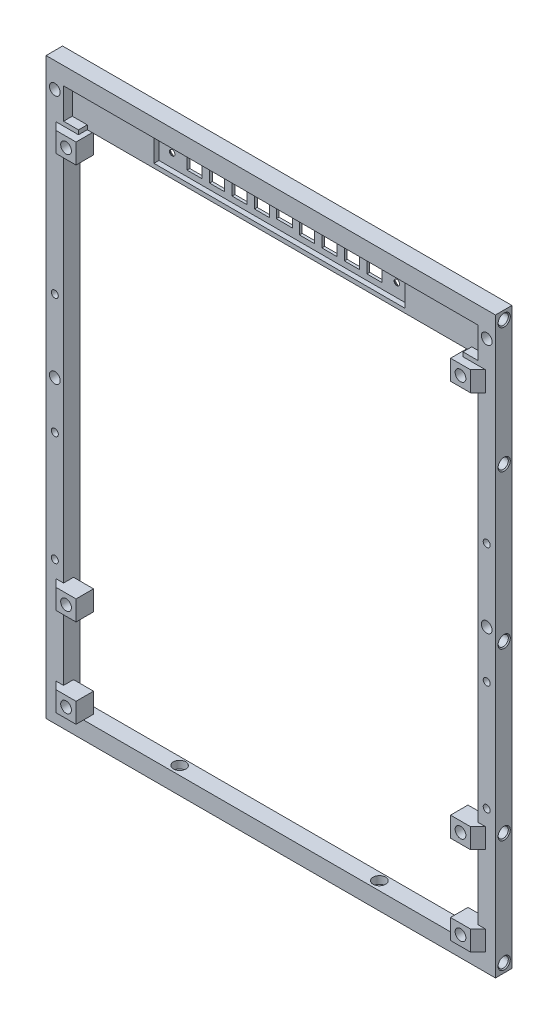
SolidWorks part; units mm, degrees
ref_plane "Front Plane" through (0, 0, 0) normal (0, 0, 1) x (1, 0, 0)
ref_plane "Top Plane" through (0, 0, 0) normal (0, 1, 0) x (1, 0, 0)
ref_plane "Right Plane" through (0, 0, 0) normal (1, 0, 0) x (0, 0, -1)
sketch "Sketch1" plane through (0, 0, 0) normal (0, 0, 1) x (1, 0, 0)
  line L1 (-90, -115) -> (90, -115)
  line L2 (-90, -115) -> (-90, 115)
  line L3 (-90, 115) -> (90, 115)
  line L4 (90, -115) -> (90, 115)
  line L5 (-90, -115) -> (90, 115) construction
  line L6 (-90, 115) -> (90, -115) construction
  line L7 (-83, -108) -> (83, -108)
  line L8 (-83, -108) -> (-83, 108)
  line L9 (-83, 108) -> (83, 108)
  line L10 (83, -108) -> (83, 108)
  line L11 (-83, -108) -> (83, 108) construction
  line L12 (-83, 108) -> (83, -108) construction
  point P0 (0, 0)
  point P6 (0, 0)
  dimension "D1" = 180
  dimension "D2" = 230
  dimension "D3" = 7
  dimension "D4" = 7
extrude "Boss-Extrude1" add sketch "Sketch1" along normal blind 7
sketch "Sketch2" plane through (-90, 0, 0) normal (-1, 0, 0) x (0, 0, 1)
  line L0 (3.5, 111.5) -> (3.5, -111.5) construction
  line L1 (7, 115) -> (0, 115) construction
  circle A0 centre (3.5, -111.5) radius 2.05
  circle A2 centre (3.5, 111.5) radius 2.05
  circle A3 centre (3.5, 61.5) radius 2.05
  circle A4 centre (3.5, -66.5) radius 2.05
  point P2 (3.5, 0)
  point P7 (3.5, 115)
  dimension "D2" = 4.1
  dimension "D3" = 50
  dimension "D4" = 45
  dimension "D1" = 3.5
extrude "Cut-Extrude1" cut sketch "Sketch2" against normal blind 6
mirror "Mirror1" about plane through (0, 0, 0) normal (1, 0, 0) of "Cut-Extrude1"
sketch "Sketch3" plane through (0, -108, 0) normal (0, 1, 0) x (1, 0, 0)
  line L0 (0, 0) -> (0, -7) construction
  line L1 (-83, 0) -> (83, 0) construction
  line L2 (-83, -7) -> (83, -7) construction
  line L3 (40, -3.5) -> (-40, -3.5) construction
  circle A0 centre (40, -3.5) radius 1.35
  circle A1 centre (-40, -3.5) radius 1.35
  point P9 (0, -3.5)
  dimension "D1" = 2.7
  dimension "D2" = 80
extrude "Cut-Extrude2" cut sketch "Sketch3" against normal through all
sketch "Sketch4" plane through (0, -108, 0) normal (0, 1, 0) x (1, 0, 0)
  circle A0 centre (40, -3.5) radius 2.5
  circle A1 centre (-40, -3.5) radius 2.5
  dimension "D1" = 5
extrude "Cut-Extrude3" cut sketch "Sketch4" against normal blind 3
sketch "Sketch5" plane through (0, 0, 0) normal (0, 0, -1) x (-1, 0, 0)
  line L0 (-86.5, -115) -> (-86.5, 115) construction
  line L1 (90, -115) -> (-90, -115) construction
  line L2 (-90, 115) -> (90, 115) construction
  line L3 (-83, 0) -> (-90, 0) construction
  line L4 (-83, -108) -> (-83, 108) construction
  line L5 (-90, -115) -> (-90, 115) construction
  line L6 (0, 115) -> (0, -115) construction
  line L7 (83, -108) -> (-83, -108) construction
  circle A0 centre (-86.5, 34) radius 1.4
  circle A1 centre (86.5, 34) radius 1.4
  circle A2 centre (-86.5, -58) radius 1.4
  circle A3 centre (86.5, -58) radius 1.4
  point P12 (-86.5, 0)
  point P13 (-86.5, 0)
  dimension "D1" = 2.8
  dimension "D2" = 34
  dimension "D3" = 50
extrude "Cut-Extrude4" cut sketch "Sketch5" against normal through all
sketch "Sketch6" plane through (0, 0, 0) normal (0, 0, -1) x (-1, 0, 0)
  circle A0 centre (-86.5, 34) radius 2.5
  circle A1 centre (86.5, 34) radius 2.5
  circle A2 centre (-86.5, -58) radius 2.5
  circle A3 centre (86.5, -58) radius 2.5
  dimension "D1" = 5
extrude "Cut-Extrude5" cut sketch "Sketch6" against normal blind 3
sketch "Sketch7" plane through (0, 0, 0) normal (0, 0, -1) x (-1, 0, 0)
  line L0 (-83, 108) -> (-90, 108) construction
  line L1 (-90, -115) -> (-90, 115) construction
  line L2 (-86.5, 105) -> (-86.5, 5) construction
  line L3 (-90, 115) -> (90, 115) construction
  circle A0 centre (-86.5, 105) radius 2.15
  circle A1 centre (-86.5, 5) radius 2.15
  point P8 (-86.5, 108)
  dimension "D1" = 4.3
  dimension "D2" = 10
  dimension "D3" = 100
extrude "Cut-Extrude6" cut sketch "Sketch7" against normal through all
mirror "Mirror2" about plane through (0, 0, 0) normal (1, 0, 0) of "Cut-Extrude6"
sketch "Sketch8" plane through (0, 0, 3) normal (0, 0, -1) x (-1, 0, 0)
  line L2 (-87.9, 31.9288) -> (-87.9, 36.0712)
  line L4 (-85.1, 31.9288) -> (-85.1, 36.0712)
  line L5 (-87.9, 31.9288) -> (-85.1, 36.0712) construction
  line L6 (-87.9, 36.0712) -> (-85.1, 31.9288) construction
  line L8 (-87.9, -60.0712) -> (-87.9, -55.9288)
  line L10 (-85.1, -60.0712) -> (-85.1, -55.9288)
  line L11 (-87.9, -60.0712) -> (-85.1, -55.9288) construction
  line L12 (-87.9, -55.9288) -> (-85.1, -60.0712) construction
  circle A0 centre (-86.5, 34) radius 2.5 construction
  circle A1 centre (-86.5, -58) radius 2.5 construction
  circle A2 centre (-86.5, -58) radius 2.5 construction
  arc A3 (-85.1, 36.0712) -> (-87.9, 36.0712) centre (-86.5, 34) ccw
  arc A4 (-85.1, -55.9288) -> (-87.9, -55.9288) centre (-86.5, -58) ccw
  circle A5 centre (-86.5, 34) radius 1.4 construction
  circle A6 centre (-86.5, -58) radius 1.4 construction
  arc A7 (-87.9, -60.0712) -> (-85.1, -60.0712) centre (-86.5, -58) ccw
  arc A8 (-87.9, 31.9288) -> (-85.1, 31.9288) centre (-86.5, 34) ccw
  point P0 (-86.5, 34)
  point P8 (-86.5, -58)
extrude "Cut-Extrude7" cut sketch "Sketch8" against normal blind 0.2
sketch "Sketch9" plane through (0, 0, 3.2) normal (0, 0, -1) x (-1, 0, 0)
  line L0 (-85.1, 34) -> (-85.1, 36.0712) construction
  line L1 (-87.9, 32.6) -> (-85.1, 32.6)
  line L2 (-87.9, 32.6) -> (-87.9, 35.4)
  line L3 (-87.9, 35.4) -> (-85.1, 35.4)
  line L4 (-85.1, 32.6) -> (-85.1, 35.4)
  line L5 (-87.9, 32.6) -> (-85.1, 35.4) construction
  line L6 (-87.9, 35.4) -> (-85.1, 32.6) construction
  line L7 (-85.1, -60.0712) -> (-85.1, -55.9288) construction
  line L8 (-87.9, -59.4) -> (-85.1, -59.4)
  line L9 (-87.9, -59.4) -> (-87.9, -56.6)
  line L10 (-87.9, -56.6) -> (-85.1, -56.6)
  line L11 (-85.1, -59.4) -> (-85.1, -56.6)
  line L12 (-87.9, -59.4) -> (-85.1, -56.6) construction
  line L13 (-87.9, -56.6) -> (-85.1, -59.4) construction
  arc A0 (-85.1, 34) -> (-87.9, 34) centre (-86.5, 34) ccw construction
  point P0 (-86.5, 34)
  point P8 (-86.5, -58)
extrude "Cut-Extrude8" cut sketch "Sketch9" against normal blind 0.2
mirror "Mirror3" about plane through (0, 0, 0) normal (1, 0, 0) of "Cut-Extrude8", "Cut-Extrude7"
sketch "Sketch10" plane through (0, 0, 7) normal (0, 0, 1) x (1, 0, 0)
  line L0 (83, -108) -> (83, 108) construction
  line L1 (83, -108) -> (77, -108)
  line L2 (83, -108) -> (83, -102)
  line L3 (83, -102) -> (77, -102)
  line L4 (77, -108) -> (77, -102)
  line L5 (83, -78.5) -> (77, -78.5)
  line L6 (83, -78.5) -> (83, -72.5)
  line L7 (83, -72.5) -> (77, -72.5)
  line L8 (77, -78.5) -> (77, -72.5)
  line L9 (-83, -108) -> (83, -108) construction
  dimension "D1" = 6
  dimension "D2" = 35.5
extrude "Boss-Extrude2" add sketch "Sketch10" against normal offset from surface (5.5 mm away) 1.5 up to face at (-84.35, 5, 0)
sketch "Sketch11" plane through (0, 0, 1.5) normal (0, 0, -1) x (-1, 0, 0)
  line L0 (-83, -78.5) -> (-77, -72.5) construction
  line L2 (-83, -108) -> (-77, -102) construction
  circle A0 centre (-80, -75.5) radius 1.65
  circle A1 centre (-80, -105) radius 1.65
  dimension "D1" = 3.3
extrude "Cut-Extrude9" cut sketch "Sketch11" against normal through all
mirror "Mirror4" about plane through (0, 0, 0) normal (1, 0, 0) of "Cut-Extrude9", "Boss-Extrude2"
sketch "Sketch12" plane through (0, 0, 0) normal (0, 0, -1) x (-1, 0, 0)
  line L0 (83, 108) -> (83, -108) construction
  line L1 (-83, 108) -> (83, 108)
  line L2 (-83, 108) -> (-83, 94)
  line L3 (-83, 94) -> (83, 94)
  line L4 (83, 108) -> (83, 94)
  dimension "D1" = 14
extrude "Boss-Extrude3" add sketch "Sketch12" against normal blind 1.5
sketch "Sketch13" plane through (0, 0, 1.5) normal (0, 0, 1) x (1, 0, 0)
  line L0 (-83, 108) -> (83, 94) construction
  line L2 (-50.3, 95.7) -> (50.3, 95.7)
  line L3 (-50.3, 95.7) -> (-50.3, 106.3)
  line L4 (-50.3, 106.3) -> (50.3, 106.3)
  line L5 (50.3, 95.7) -> (50.3, 106.3)
  line L6 (-50.3, 95.7) -> (50.3, 106.3) construction
  line L7 (-50.3, 106.3) -> (50.3, 95.7) construction
  line L8 (-83, 94) -> (83, 94)
  line L9 (-83, 94) -> (-83, 108)
  line L10 (-83, 108) -> (83, 108)
  line L11 (83, 94) -> (83, 108)
  line L12 (-83, 94) -> (83, 108) construction
  line L13 (-83, 108) -> (83, 94) construction
  point P4 (0, 101)
  point P9 (0, 101)
  dimension "D1" = 100.6
  dimension "D2" = 10.6
extrude "Boss-Extrude4" add sketch "Sketch13" along normal blind 2
sketch "Sketch14" plane through (0, 0, 1.5) normal (0, 0, 1) x (1, 0, 0)
  line L0 (0, 106.3) -> (0, 95.7) construction
  line L1 (50.3, 106.3) -> (-50.3, 106.3) construction
  line L2 (-50.3, 95.7) -> (50.3, 95.7) construction
  line L3 (-50.3, 101) -> (50.3, 101) construction
  line L4 (50.3, 95.7) -> (50.3, 106.3) construction
  line L5 (-33, 104) -> (-39, 104)
  line L6 (-3.25, 99) -> (3.25, 99)
  line L7 (-3.25, 99) -> (-3.25, 103)
  line L8 (-3.25, 103) -> (3.25, 103)
  line L9 (3.25, 99) -> (3.25, 103)
  line L10 (-3.25, 99) -> (3.25, 103) construction
  line L11 (-3.25, 103) -> (3.25, 99) construction
  line L12 (6, 98) -> (12, 98)
  line L13 (6, 98) -> (6, 104)
  line L14 (6, 104) -> (12, 104)
  line L15 (12, 98) -> (12, 104)
  line L16 (6, 98) -> (12, 104) construction
  line L17 (6, 104) -> (12, 98) construction
  line L18 (15, 98) -> (21, 98)
  line L19 (15, 98) -> (15, 104)
  line L20 (15, 104) -> (21, 104)
  line L21 (21, 98) -> (21, 104)
  line L22 (15, 98) -> (21, 104) construction
  line L23 (15, 104) -> (21, 98) construction
  line L24 (24, 98) -> (30, 98)
  line L25 (24, 98) -> (24, 104)
  line L26 (24, 104) -> (30, 104)
  line L27 (30, 98) -> (30, 104)
  line L28 (24, 98) -> (30, 104) construction
  line L29 (24, 104) -> (30, 98) construction
  line L30 (33, 98) -> (39, 98)
  line L31 (33, 98) -> (33, 104)
  line L32 (33, 104) -> (39, 104)
  line L33 (39, 98) -> (39, 104)
  line L34 (33, 98) -> (39, 104) construction
  line L35 (33, 104) -> (39, 98) construction
  line L36 (-39, 98) -> (-39, 104)
  line L37 (-33, 98) -> (-39, 98)
  line L38 (-33, 98) -> (-33, 104)
  line L39 (-24, 104) -> (-30, 104)
  line L40 (-30, 98) -> (-30, 104)
  line L41 (-24, 98) -> (-30, 98)
  line L42 (-24, 98) -> (-24, 104)
  line L43 (-15, 104) -> (-21, 104)
  line L44 (-21, 98) -> (-21, 104)
  line L45 (-15, 98) -> (-21, 98)
  line L46 (-15, 98) -> (-15, 104)
  line L47 (-6, 104) -> (-12, 104)
  line L48 (-12, 98) -> (-12, 104)
  line L49 (-6, 98) -> (-12, 98)
  line L50 (-6, 98) -> (-6, 104)
  circle A0 centre (-45, 101) radius 1.3 construction
  circle A1 centre (45, 101) radius 1.3 construction
  point P6 (0, 101)
  point P11 (0, 101)
  point P16 (9, 101)
  point P21 (18, 101)
  point P26 (27, 101)
  point P31 (36, 101)
  dimension "D10" = 2.6
  dimension "D9" = 45
  dimension "D1" = 6.5
  dimension "D2" = 4
  dimension "D3" = 6
  dimension "D4" = 9
  dimension "D5" = 9
  dimension "D6" = 9
  dimension "D7" = 9
  dimension "D8" = 45
extrude "Cut-Extrude10" cut sketch "Sketch14" against normal through all
sketch "Sketch15" plane through (0, 0, 1.5) normal (0, 0, 1) x (1, 0, 0)
  circle A0 centre (-45, 101) radius 1
  circle A1 centre (45, 101) radius 1
  dimension "D1" = 2
extrude "Boss-Extrude5" add sketch "Sketch15" along normal up to surface (2 mm away) up to face at (0, 101, 3.5)
chamfer "Chamfer1" distance 0.4 angle 45 3 edges at (-83, -7, 0) (83, -7, 0) (0, -108, 0) tangent propagation no
chamfer "Chamfer2" distance 0.4 angle 45 4 edges at (0, 115, 0) (-90, 0, 0) (0, -115, 0) (90, 0, 0)
chamfer "Chamfer3" distance 0.4 angle 45 36 edges at (-36, 98, 0) (-39, 101, 0) (-36, 104, 0) (-33, 101, 0) (-27, 98, 0) (-30, 101, 0) (-27, 104, 0) (-24, 101, 0) (-18, 98, 0) (-21, 101, 0) (-18, 104, 0) (-15, 101, 0) (-9, 98, 0) (-12, 101, 0) (-9, 104, 0) (-6, 101, 0) (0, 99, 0) (-3.25, 101, 0) (0, 103, 0) (3.25, 101, 0) (9, 98, 0) (6, 101, 0) (9, 104, 0) (12, 101, 0) (18, 98, 0) (15, 101, 0) (18, 104, 0) (21, 101, 0) (36, 98, 0) (33, 101, 0) (36, 104, 0) (39, 101, 0) (27, 98, 0) (24, 101, 0) (27, 104, 0) (30, 101, 0)
sketch "Sketch16" plane through (0, 0, 7) normal (0, 0, 1) x (1, 0, 0)
  line L0 (-77, 94) -> (-77, 95.7)
  line L1 (-83, -72.5) -> (-77, -72.5)
  line L2 (-83, -72.5) -> (-83, -66.5)
  line L3 (-83, -66.5) -> (-77, -66.5)
  line L4 (-77, -72.5) -> (-77, -66.5)
  line L5 (83, -72.5) -> (77, -72.5)
  line L6 (83, -72.5) -> (83, -66.5)
  line L7 (83, -66.5) -> (77, -66.5)
  line L8 (77, -72.5) -> (77, -66.5)
  line L9 (83, 94) -> (77, 94) construction
  line L10 (83, 94) -> (83, 88)
  line L11 (83, 88) -> (77, 88)
  line L12 (77, 94) -> (77, 88)
  line L13 (-83, 94) -> (-77, 94) construction
  line L14 (-83, 94) -> (-83, 88)
  line L15 (-83, 88) -> (-77, 88)
  line L16 (-77, 94) -> (-77, 88)
  line L17 (-50.3, 95.7) -> (50.3, 95.7) construction
  line L18 (-77, 95.7) -> (-83, 95.7)
  line L19 (-83, 108) -> (-83, 94) construction
  line L20 (-83, 95.7) -> (-83, 94)
  line L21 (77, 94) -> (77, 95.7)
  line L22 (77, 95.7) -> (83, 95.7)
  line L23 (83, 94) -> (83, 108) construction
  line L24 (83, 95.7) -> (83, 94)
  dimension "D1" = 6
extrude "Boss-Extrude7" add sketch "Sketch16" against normal offset from surface (5.5 mm away) 1.5 up to face at (-36, 101, 0)
sketch "Sketch17" plane through (0, 0, 1.5) normal (0, 0, -1) x (-1, 0, 0)
  line L0 (-77, 88) -> (77, -66.5) construction
  line L1 (-77, -66.5) -> (-77, -78.5) construction
  line L2 (-80, -69.5) -> (80, -69.5) construction
  line L3 (-80, -69.5) -> (-80, 91) construction
  line L4 (-80, 91) -> (80, 91) construction
  line L5 (80, -69.5) -> (80, 91) construction
  line L6 (-80, -69.5) -> (80, 91) construction
  line L7 (-80, 91) -> (80, -69.5) construction
  line L8 (77, -66.5) -> (83, -66.5) construction
  circle A0 centre (-80, -69.5) radius 1.65
  circle A1 centre (80, -69.5) radius 1.65
  circle A2 centre (80, 91) radius 1.65
  circle A3 centre (-80, 91) radius 1.65
  point P4 (0, 10.75)
  dimension "D3" = 3.3
  dimension "D1" = 3
  dimension "D2" = 3
extrude "Cut-Extrude11" cut sketch "Sketch17" against normal through all
sketch "Sketch18" plane through (0, 0, 1.5) normal (0, 0, 1) x (1, 0, 0)
  circle A0 centre (-45, 101) radius 1.1
  circle A1 centre (45, 101) radius 1.1
  dimension "D1" = 2.2
extrude "Cut-Extrude12" cut sketch "Sketch18" against normal through all both and the other way through all
chamfer "Chamfer4" distance 1.3 angle 45 2 edges at (-43.9, 101, 0) (46.1, 101, 0)
sketch "Sketch19" plane through (0, 0, 1.5) normal (0, 0, -1) x (-1, 0, 0)
  line L1 (-83, -108) -> (83, -108)
  line L2 (-83, -108) -> (-83, 94)
  line L3 (-83, 94) -> (83, 94)
  line L4 (83, -108) -> (83, 94)
extrude "Cut-Extrude13" cut sketch "Sketch19" against normal through all
ref_plane "Plane1" through (0, 0, 3) normal (0, 0, 1) x (1, 0, 0)
sketch "Sketch20" plane through (0, 0, 3) normal (0, 0, 1) x (1, 0, 0)
  line L0 (83, 94) -> (83, -108) construction
  line L1 (83, -108) -> (75, -108)
  line L2 (83, -108) -> (83, -100)
  line L3 (83, -100) -> (75, -100)
  line L4 (75, -108) -> (75, -100)
  line L5 (83, 94) -> (75, 94)
  line L6 (83, 94) -> (83, 86)
  line L7 (83, 86) -> (75, 86)
  line L8 (75, 94) -> (75, 86)
  line L9 (83, -64.5) -> (75, -64.5)
  line L10 (83, -64.5) -> (83, -72.5)
  line L11 (83, -72.5) -> (75, -72.5)
  line L12 (75, -64.5) -> (75, -72.5)
  dimension "D1" = 8
  dimension "D2" = 27.5
extrude "Boss-Extrude8" add sketch "Sketch20" along normal blind 7
sketch "Sketch21" plane through (0, 0, 3) normal (0, 0, -1) x (-1, 0, 0)
  line L0 (-75, 94) -> (-83, 86) construction
  line L1 (-83, -100) -> (-75, -108) construction
  line L2 (-83, -64.5) -> (-75, -72.5) construction
  circle A0 centre (-79, 90) radius 2.15
  circle A1 centre (-79, -104) radius 2.15
  circle A2 centre (-79, -68.5) radius 2.15
  dimension "D1" = 4.3
extrude "Cut-Extrude14" cut sketch "Sketch21" against normal through all
mirror "Mirror5" about plane through (0, 0, 0) normal (1, 0, 0) of "Cut-Extrude14", "Boss-Extrude8"
chamfer "Chamfer5" distance 3 angle 45 6 edges at (-83, -104, 7) (83, -104, 7) (83, 90, 7) (-83, 90, 7) (-83, -68.5, 7) (83, -68.5, 7)
sketch "Sketch23" plane through (0, 0, 0) normal (0, 0, -1) x (-1, 0, 0)
  line L0 (-83.4, 94) -> (83.4, 94) construction
  line L1 (-15, 94) -> (15, 94)
  line L2 (-15, 94) -> (-15, 69)
  line L3 (-15, 69) -> (15, 69)
  line L4 (15, 94) -> (15, 69)
  point P6 (0, 69)
  dimension "D1" = 25
  dimension "D2" = 30
extrude "Boss-Extrude10" add sketch "Sketch23" against normal up to surface (3.5 mm away) up to face at (0, 97.48, 3.5)
sketch "Sketch24" plane through (0, 0, 3.5) normal (0, 0, 1) x (1, 0, 0)
  line L0 (15, 69) -> (-15, 69) construction
  line L1 (-12.7, 69) -> (12.7, 69)
  line L2 (-12.7, 69) -> (-12.7, 94)
  line L3 (-12.7, 94) -> (12.7, 94)
  line L4 (12.7, 69) -> (12.7, 94)
  line L5 (-75, 94) -> (-15, 94) construction
  point P6 (0, 69)
  dimension "D1" = 25.4
extrude "Cut-Extrude15" cut sketch "Sketch24" against normal offset from surface (2.5 mm away) 1 up to face at (-47.4, 101, 0)
sketch "Sketch26" plane through (0, 0, 1) normal (0, 0, 1) x (1, 0, 0)
  line L0 (12.7, 94) -> (-12.7, 94) construction
  line L1 (-12.5, 93.4) -> (12.5, 93.4) construction
  line L2 (-12.5, 93.4) -> (-12.5, 69.538) construction
  line L3 (-12.5, 69.538) -> (12.5, 69.538) construction
  line L4 (12.5, 93.4) -> (12.5, 69.538) construction
  line L5 (0, 93.4) -> (0, 69.538) construction
  line L6 (-10.5, 91.4) -> (10.5, 91.4) construction
  line L7 (-10.5, 91.4) -> (-10.5, 78.9) construction
  line L8 (-10.5, 78.9) -> (10.5, 78.9) construction
  line L9 (10.5, 91.4) -> (10.5, 78.9) construction
  line L10 (12.7, 94) -> (-12.7, 94) construction
  line L11 (-5.4, 73.6) -> (5.4, 73.6) construction
  line L12 (-5.4, 73.6) -> (-5.4, 84.4) construction
  line L13 (-5.4, 84.4) -> (5.4, 84.4) construction
  line L14 (5.4, 73.6) -> (5.4, 84.4) construction
  line L15 (-5.4, 73.6) -> (5.4, 84.4) construction
  line L16 (-5.4, 84.4) -> (5.4, 73.6) construction
  circle A0 centre (-10.5, 91.4) radius 1.1 construction
  circle A1 centre (10.5, 91.4) radius 1.1 construction
  circle A2 centre (10.5, 78.9) radius 1.1 construction
  circle A3 centre (-10.5, 78.9) radius 1.1 construction
  point P4 (0, 93.4)
  point P7 (0, 94)
  point P12 (0, 91.4)
  point P19 (0, 79)
  dimension "D3" = 2.2
  dimension "D1" = 25
  dimension "D2" = 23.862
  dimension "D4" = 2
  dimension "D5" = 14.5
  dimension "D6" = 10.8
  dimension "D7" = 10.8
  dimension "D8" = 14.4
  dimension "D9" = 0.6
  dimension "D10" = 2
sketch "Sketch27" plane through (0, 0, 1) normal (0, 0, 1) x (1, 0, 0)
  line L0 (-12.7, 94) -> (-12.7, 69) construction
  line L1 (-12.7, 94) -> (-8.5, 94)
  line L2 (-12.7, 94) -> (-12.7, 89.4)
  line L3 (-12.7, 89.4) -> (-8.5, 89.4)
  line L4 (-8.5, 94) -> (-8.5, 89.4)
  line L5 (-12.7, 76.9) -> (-8.5, 76.9)
  line L6 (-12.7, 76.9) -> (-12.7, 80.9)
  line L7 (-12.7, 80.9) -> (-8.5, 80.9)
  line L8 (-8.5, 76.9) -> (-8.5, 80.9)
  line L9 (0, 94) -> (0, 69) construction
  line L10 (12.7, 94) -> (-12.7, 94) construction
  line L11 (-12.7, 69) -> (12.7, 69) construction
  line L12 (8.5, 76.9) -> (8.5, 80.9)
  line L13 (12.7, 80.9) -> (8.5, 80.9)
  line L14 (12.7, 76.9) -> (12.7, 80.9)
  line L15 (12.7, 76.9) -> (8.5, 76.9)
  line L16 (8.5, 94) -> (8.5, 89.4)
  line L17 (12.7, 89.4) -> (8.5, 89.4)
  line L18 (12.7, 94) -> (12.7, 89.4)
  line L19 (12.7, 94) -> (8.5, 94)
  dimension "D1" = 2
  dimension "D2" = 2
  dimension "D3" = 2
  dimension "D4" = 2
  dimension "D5" = 2
extrude "Boss-Extrude11" add sketch "Sketch27" along normal blind 3
sketch "Sketch28" plane through (0, 0, 1) normal (0, 0, 1) x (1, 0, 0)
  line L0 (-5.4, 84.4) -> (5.4, 84.4) construction
  line L1 (-6, 73) -> (6, 73)
  line L2 (-6, 73) -> (-6, 85)
  line L3 (-6, 85) -> (6, 85)
  line L4 (6, 73) -> (6, 85)
  line L5 (-6, 73) -> (6, 85) construction
  line L6 (-6, 85) -> (6, 73) construction
  line L7 (5.4, 73.6) -> (5.4, 84.4) construction
  point P0 (0, 79)
  dimension "D1" = 0.6
  dimension "D2" = 0.6
extrude "Cut-Extrude16" cut sketch "Sketch28" against normal through all
sketch "Sketch29" plane through (0, 0, 4) normal (0, 0, 1) x (1, 0, 0)
  circle A0 centre (-10.5, 78.9) radius 1.1
  circle A1 centre (-10.5, 91.4) radius 1.1
  circle A2 centre (10.5, 91.4) radius 1.1
  circle A3 centre (10.5, 78.9) radius 1.1
  dimension "D1" = 2.2
extrude "Cut-Extrude17" cut sketch "Sketch29" against normal through all
chamfer "Chamfer6" distance 1.3 angle 45 4 edges at (11.6, 78.9, 0) (-9.4, 78.9, 0) (-9.4, 91.4, 0) (11.6, 91.4, 0)
chamfer "Chamfer7" distance 0.4 angle 45 4 edges at (0, 73, 0) (-6, 79, 0) (0, 85, 0) (6, 79, 0)
chamfer "Chamfer8" distance 0.4 angle 45 2 edges at (-49.2, 94, 0) (49.2, 94, 0)
sketch "Sketch30" plane through (0, 0, 3.5) normal (0, 0, 1) x (1, 0, 0)
  line L0 (-12.7, 69) -> (-12.7, 94)
  line L1 (-12.7, 94) -> (12.7, 94)
  line L2 (12.7, 94) -> (12.7, 69)
  line L3 (12.7, 69) -> (15, 69)
  line L4 (15, 69) -> (15, 95.7)
  line L5 (-50.3, 95.7) -> (50.3, 95.7) construction
  line L6 (15, 95.7) -> (-15, 95.7)
  line L7 (-15, 95.7) -> (-15, 69)
  line L8 (-12.7, 69) -> (-15, 69)
extrude "Boss-Extrude12" add sketch "Sketch30" along normal blind 3
chamfer "Chamfer9" distance 0.4 angle 45 18 edges at (-76.85, -104, 3) (-84.35, 5, 0) (-76.85, -68.5, 3) (-76.85, 90, 3) (-84.35, 105, 0) (76.85, -104, 3) (76.85, -68.5, 3) (76.85, 90, 3) (84.35, 5, 0) (84.35, 105, 0) (90, 111.5, 5.55) (90, 61.5, 5.55) (90, -66.5, 5.55) (90, -111.5, 5.55) (-90, -111.5, 5.55) (-90, -66.5, 5.55) (-90, 61.5, 5.55) (-90, 111.5, 5.55)
sketch "Sketch31" plane through (0, 0, 0) normal (0, 0, -1) x (-1, 0, 0)
  line L1 (-15, 69) -> (15, 69)
  line L2 (-15, 69) -> (-15, 94)
  line L3 (-15, 94) -> (15, 94)
  line L4 (15, 69) -> (15, 94)
extrude "Cut-Extrude18" cut sketch "Sketch31" against normal through all
sketch "Sketch32" plane through (-15, 0, 0) normal (-1, 0, 0) x (0, 0, 1)
  line L4 (3.5, 94) -> (6.5, 94)
  line L5 (6.5, 94) -> (6.5, 95.7)
  line L6 (6.5, 95.7) -> (3.5, 95.7)
  line L7 (3.5, 95.7) -> (3.5, 94)
  line L8 (3.5, 94) -> (6.5, 94)
  line L9 (6.5, 94) -> (6.5, 95.7)
  line L10 (6.5, 95.7) -> (3.5, 95.7)
  line L11 (3.5, 95.7) -> (3.5, 94)
  dimension "D1" = 0
extrude "Cut-Extrude19" cut sketch "Sketch32" against normal up to surface (30 mm away) up to face at (15, 94.85, 5)
chamfer "Chamfer10" distance 0.4 angle 45 1 edges at (0, 94, 0)
sketch "Sketch33" plane through (0, 0, 0) normal (0, 0, -1) x (-1, 0, 0)
  line L0 (90, -115) -> (-90, -115) construction
  circle A0 centre (-86.5, -14) radius 1.4
  arc A1 (-87.9, 34) -> (-86.5, 32.6) centre (-86.5, 34) ccw construction
  point P3 (-86.5, 34)
  dimension "D1" = 101
extrude "Cut-Extrude20" cut sketch "Sketch33" against normal through all
mirror "Mirror6" about plane through (0, 0, 0) normal (1, 0, 0) of "Cut-Extrude20"
sketch "Sketch34" plane through (0, 0, 0) normal (0, 0, -1) x (-1, 0, 0)
  circle A0 centre (-86.5, -14) radius 2.5
  circle A1 centre (-86.5, -58) radius 2.5 construction
extrude "Cut-Extrude21" cut sketch "Sketch34" against normal up to surface (3 mm away) up to face at (84.55, -58, 3)
sketch "Sketch35" plane through (0, 0, 3) normal (0, 0, -1) x (-1, 0, 0)
  line L2 (-87.9, -16.0712) -> (-87.9, -11.9288)
  line L4 (-85.1, -16.0712) -> (-85.1, -11.9288)
  line L5 (-87.9, -16.0712) -> (-85.1, -11.9288) construction
  line L6 (-87.9, -11.9288) -> (-85.1, -16.0712) construction
  circle A0 centre (-86.5, -14) radius 2.5 construction
  circle A1 centre (-86.5, -14) radius 1.4 construction
  circle A2 centre (-86.5, -14) radius 2.5 construction
  arc A3 (-85.1, -11.9288) -> (-87.9, -11.9288) centre (-86.5, -14) ccw
  arc A4 (-87.9, -16.0712) -> (-85.1, -16.0712) centre (-86.5, -14) ccw
  point P0 (-86.5, -14)
extrude "Cut-Extrude22" cut sketch "Sketch35" against normal blind 0.2
sketch "Sketch36" plane through (0, 0, 3.2) normal (0, 0, -1) x (-1, 0, 0)
  line L0 (-85.1, -16.0712) -> (-85.1, -11.9288) construction
  line L1 (-87.9, -15.4) -> (-85.1, -15.4)
  line L2 (-87.9, -15.4) -> (-87.9, -12.6)
  line L3 (-87.9, -12.6) -> (-85.1, -12.6)
  line L4 (-85.1, -15.4) -> (-85.1, -12.6)
  line L5 (-87.9, -15.4) -> (-85.1, -12.6) construction
  line L6 (-87.9, -12.6) -> (-85.1, -15.4) construction
  arc A0 (-85.1, -14) -> (-87.9, -14) centre (-86.5, -14) ccw construction
  point P0 (-86.5, -14)
extrude "Cut-Extrude23" cut sketch "Sketch36" against normal blind 0.2
mirror "Mirror7" about plane through (0, 0, 0) normal (1, 0, 0) of "Cut-Extrude23", "Cut-Extrude22", "Cut-Extrude21"
sketch "Sketch37" plane through (-90, 0, 0) normal (-1, 0, 0) x (0, 0, 1)
  circle A0 centre (3.5, 0) radius 2.05
  circle A1 centre (3.5, 61.5) radius 2.05 construction
  point P3 (3.5, 61.5)
  dimension "D1" = 61.5
extrude "Cut-Extrude24" cut sketch "Sketch37" against normal blind 6
chamfer "Chamfer11" distance 0.4 angle 45 1 edges at (-90, 0, 5.55)
mirror "Mirror10" about plane through (0, 0, 0) normal (1, 0, 0) of "Cut-Extrude24"
chamfer "Chamfer12" distance 0.4 angle 45 1 edges at (90, 0, 5.55)
